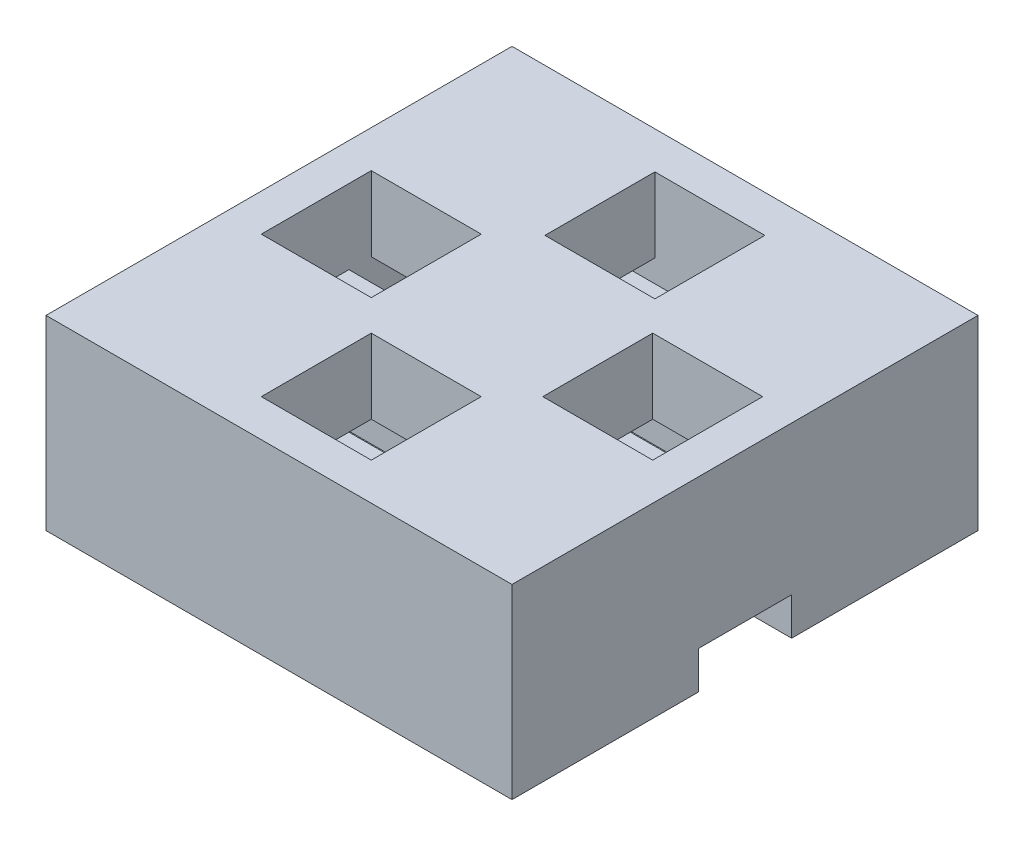
SolidWorks part; units mm, degrees
ref_plane "Front Plane" through (0, 0, 0) normal (0, 0, 1) x (1, 0, 0)
ref_plane "Top Plane" through (0, 0, 0) normal (0, 1, 0) x (1, 0, 0)
ref_plane "Right Plane" through (0, 0, 0) normal (1, 0, 0) x (0, 0, -1)
sketch "Sketch1" plane through (0, 0, 0) normal (0, 1, 0) x (1, 0, 0)
  line L1 (-25, 25) -> (25, 25)
  line L2 (-25, 25) -> (-25, -25)
  line L3 (-25, -25) -> (25, -25)
  line L4 (25, 25) -> (25, -25)
  line L5 (-25, 25) -> (25, -25) construction
  line L6 (-25, -25) -> (25, 25) construction
  line L7 (-5.668, 21) -> (6.132, 21)
  line L8 (-5.668, 21) -> (-5.668, 9.2)
  line L9 (-5.668, 9.2) -> (6.132, 9.2)
  line L10 (6.132, 21) -> (6.132, 9.2)
  line L11 (-5.668, 21) -> (6.132, 9.2) construction
  line L12 (-5.668, 9.2) -> (6.132, 21) construction
  line L13 (9.2, 5.9) -> (21, 5.9)
  line L14 (9.2, 5.9) -> (9.2, -5.9)
  line L15 (9.2, -5.9) -> (21, -5.9)
  line L16 (21, 5.9) -> (21, -5.9)
  line L17 (9.2, 5.9) -> (21, -5.9) construction
  line L18 (9.2, -5.9) -> (21, 5.9) construction
  line L19 (-21, 5.9) -> (-9.2, 5.9)
  line L20 (-21, 5.9) -> (-21, -5.9)
  line L21 (-21, -5.9) -> (-9.2, -5.9)
  line L22 (-9.2, 5.9) -> (-9.2, -5.9)
  line L23 (-21, 5.9) -> (-9.2, -5.9) construction
  line L24 (-21, -5.9) -> (-9.2, 5.9) construction
  line L25 (5.9, -21) -> (-5.9, -21)
  line L26 (5.9, -21) -> (5.9, -9.2)
  line L27 (5.9, -9.2) -> (-5.9, -9.2)
  line L28 (-5.9, -21) -> (-5.9, -9.2)
  line L29 (5.9, -21) -> (-5.9, -9.2) construction
  line L30 (5.9, -9.2) -> (-5.9, -21) construction
  point P0 (0, 0)
  point P6 (0.232, 15.1)
  point P11 (15.1, 0)
  point P16 (-15.1, 0)
  point P21 (0, -15.1)
  dimension "D1" = 50
  dimension "D2" = 50
  dimension "D3" = 11.8
  dimension "D4" = 11.8
  dimension "D5" = 11.8
  dimension "D6" = 11.8
  dimension "D7" = 11.8
  dimension "D8" = 11.8
  dimension "D9" = 11.8
  dimension "D10" = 11.8
  dimension "D11" = 4
  dimension "D12" = 4
  dimension "D13" = 4
  dimension "D14" = 4
  dimension "D15" = 25
  dimension "D16" = 25
extrude "Boss-Extrude1" add sketch "Sketch1" along normal blind 8
sketch "Sketch2" plane through (0, 0, 0) normal (0, -1, 0) x (1, 0, 0)
  line L0 (-5.9, 21) -> (-21, 21)
  line L1 (-11.8, 18.6) -> (11.8, 18.6)
  line L2 (-11.8, 18.6) -> (-11.8, 11.6)
  line L3 (-11.8, 11.6) -> (11.8, 11.6)
  line L4 (11.8, 18.6) -> (11.8, 11.6)
  line L5 (-11.8, 18.6) -> (11.8, 11.6) construction
  line L6 (-11.8, 11.6) -> (11.8, 18.6) construction
  line L12 (-21, 3.5) -> (21, 3.5)
  line L17 (-21, 3.5) -> (-21, -3.5)
  line L18 (-21, -3.5) -> (21, -3.5)
  line L19 (-11.568, -11.6) -> (12.032, -11.6)
  line L20 (-11.568, -11.6) -> (-11.568, -18.6)
  line L21 (-11.568, -18.6) -> (12.032, -18.6)
  line L22 (12.032, -11.6) -> (12.032, -18.6)
  line L23 (-11.568, -11.6) -> (12.032, -18.6) construction
  line L24 (-11.568, -18.6) -> (12.032, -11.6) construction
  line L25 (-21, -21) -> (-21, 21)
  line L26 (21, -21) -> (-21, -21)
  line L27 (-5.9, 21) -> (21, 21)
  line L28 (21, -21) -> (21, 21)
  line L31 (-5.9, 9.2) -> (-5.9, 21) construction
  line L32 (5.9, 9.2) -> (-5.9, 9.2) construction
  line L33 (-5.668, -21) -> (-5.668, -9.2) construction
  line L36 (21, 3.5) -> (21, -3.5)
  line L37 (-21, 3.5) -> (21, -3.5) construction
  line L38 (-21, -3.5) -> (21, 3.5) construction
  point P0 (0, 15.1)
  point P5 (-15.2275, 0.8547)
  point P6 (0, 0)
  point P10 (14.3332, 1.7102)
  point P15 (0.232, -15.1)
  point P40 (-5.668, -15.1)
  line M21 (-21, -5.9) -> (-21, 5.9)
  line M24 (6.132, -21) -> (-5.668, -21)
  line M27 (25, -25) -> (25, 25)
  line M28 (25, 25) -> (-25, 25)
  line M29 (-25, 25) -> (-25, -25)
  line M30 (-25, -25) -> (25, -25)
  line M31 (21, 5.9) -> (21, -5.9)
  line M36 (-5.9, 21) -> (5.9, 21)
  dimension "D1" = 23.6
  dimension "D2" = 7
  dimension "D1*(1/4)" = 5.8004
  dimension "D3" = 2.4
  dimension "D1/4" = 5.9
  dimension "D4" = 7
  dimension "D5" = 2.4
  dimension "D6" = 5.9
  dimension "D7" = 7
extrude "Boss-Extrude7" add sketch "Sketch2" along normal blind 12 contours L28 L26 L25 L0 L27 M30 M27 M28 M29 M24 M21 M36 M31 region at (0, 0, -24.2929)
extrude "Boss-Extrude8" add sketch "Sketch2<5>" along normal blind 8 contours L1 L4 L3 L2 | L12 L36 L18 L17 | L19 L22 L21 L20
sketch "Sketch2<5>" plane through (0, 0, 0) normal (0, -1, 0) x (1, 0, 0) same geometry as "Sketch2"
sketch "Sketch3" plane through (21, 0, 0) normal (-1, 0, 0) x (0, 0, 1)
  line L0 (-21, -12) -> (21, -12) construction
  line L1 (-5, -7.9569) -> (5, -7.9569)
  line L2 (-5, -7.9569) -> (-5, -12)
  line L3 (-5, -12) -> (5, -12)
  line L4 (5, -7.9569) -> (5, -12)
  line L5 (-5, -7.9569) -> (5, -12) construction
  line L6 (-5, -12) -> (5, -7.9569) construction
  line L8 (-21, -12) -> (-21, 0) construction
  point P0 (0, -9.9784)
  dimension "D1" = 10
  dimension "D2" = 21
extrude "Cut-Extrude1" cut sketch "Sketch3" against normal blind 8
